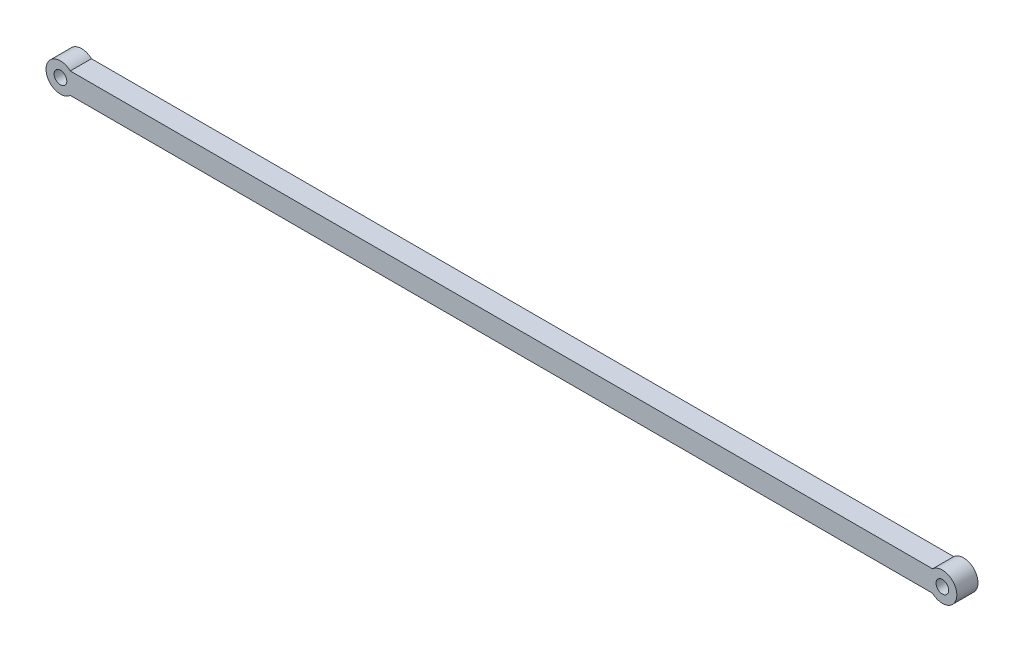
SolidWorks part; units mm, degrees
material "6061 Alloy"
ref_plane "Front Plane" through (0, 0, 0) normal (0, 0, 1) x (1, 0, 0)
ref_plane "Top Plane" through (0, 0, 0) normal (0, 1, 0) x (1, 0, 0)
ref_plane "Right Plane" through (0, 0, 0) normal (1, 0, 0) x (0, 0, -1)
sketch "Sketch3" plane through (0, 0, 0) normal (1, 0, 0) x (0, 0, -1)
  line L1 (-6.985, -6.985) -> (6.985, -6.985)
  line L2 (-6.985, -6.985) -> (-6.985, 6.985)
  line L3 (-6.985, 6.985) -> (6.985, 6.985)
  line L4 (6.985, -6.985) -> (6.985, 6.985)
  line L5 (-6.985, -6.985) -> (6.985, 6.985) construction
  line L6 (-6.985, 6.985) -> (6.985, -6.985) construction
  point P0 (0, 0)
  dimension "D1" = 13.97
extrude "Boss-Extrude1" add sketch "Sketch3" along normal blind 290.957 and the other way blind 290.957
sketch "Sketch6" plane through (0, 0, 0) normal (0, 0, 1) x (1, 0, 0)
  line L0 (290.957, 6.985) -> (290.957, -6.985) construction
  circle A0 centre (290.957, 0) radius 9.525
  dimension "D1" = 19.05
extrude "Boss-Extrude4" add sketch "Sketch6" against normal up to surface and the other way up to surface up to face at (0, 0, -6.985) other way up to face at (0, 0, 6.985)
sketch "Sketch7" plane through (0, 0, 0) normal (0, 0, 1) x (1, 0, 0)
  circle A0 centre (290.957, 0) radius 4.191
  dimension "D1" = 8.382
extrude "Cut-Extrude2" cut sketch "Sketch7" against normal through all and the other way through all
mirror "Mirror3" about plane through (0, 0, 0) normal (1, 0, 0) of "Cut-Extrude2", "Boss-Extrude4"
